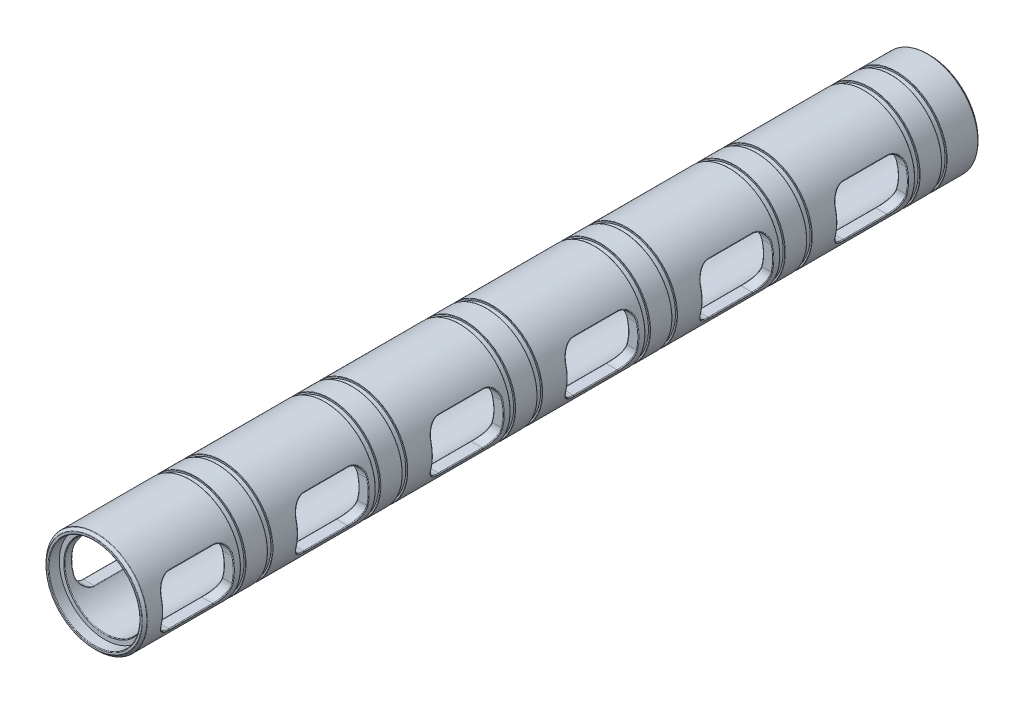
SolidWorks part; units mm, degrees
note: '?' marks a value the reader was unsure of.
ref_plane "Front Plane" through (0, 0, 0) normal (0, 0, 1) x (1, 0, 0)
ref_plane "Top Plane" through (0, 0, 0) normal (0, 1, 0) x (1, 0, 0)
ref_plane "Right Plane" through (0, 0, 0) normal (1, 0, 0) x (0, 0, -1)
ref_axis "Axis1" through (0, 0, -12.15) along (0, 0, 1)?
sketch "Sketch1" plane through (0, 0, 0) normal (0, 0, 1) x (1, 0, 0)
  circle A0 centre (0, 0) radius 15
  circle A1 centre (0, 0) radius 12
  dimension "D1" = 30
  dimension "D2" = 24
extrude "Extrude1" add sketch "Sketch1" along normal blind 248
sketch "Sketch2" plane through (0, 0, 248) normal (0, 0, 1) x (1, 0, 0)
  circle A0 centre (0, 0) radius 13.5
  dimension "D1" = 27
extrude "Cut-Extrude1" cut sketch "Sketch2" against normal blind 3.2
sketch "Sketch3" plane through (0, 0, 0) normal (0, 0, -1) x (-1, 0, 0)
  circle A0 centre (0, 0) radius 13.5
  dimension "D1" = 27
extrude "Cut-Extrude2" cut sketch "Sketch3" against normal blind 3.2
chamfer "Chamfer1" distance 0.75 angle 45 2 edges at (15, 0, 0) (15, 0, 248)
fillet "Fillet1" radius 0.2 4 edges at (12, 0, 244.8) (13.5, 0, 248) (-12, 0, 3.2) (-13.5, 0, 0)
sketch "Sketch5" plane through (0, 0, 0) normal (0, 0, -1) x (-1, 0, 0)
  circle A0 centre (0, 0) radius 15
  circle A1 centre (0, 0) radius 14.5
  circle A2 centre (0, 0) radius 15 construction
  dimension "D1" = 29
extrude "Cut-Extrude3" cut sketch "Sketch5" along normal blind 1.5 from offset 11.5
sketch "Sketch6" plane through (0, 0, 0) normal (0, 0, -1) x (-1, 0, 0)
  circle A0 centre (0, 0) radius 15
  circle A1 centre (0, 0) radius 14.5
  circle A2 centre (0, 0) radius 14.5 construction
  circle A4 centre (0, 0) radius 15 construction
extrude "Cut-Extrude4" cut sketch "Sketch6" against normal blind 1.5 from offset 18
fillet "Fillet2" radius 0.1 4 edges at (-15, 0, 10) (-15, 0, 11.5) (-15, 0, 19.5) (-15, 0, 18)
sketch "Sketch7" plane through (0, 0, 0) normal (1, 0, 0) x (0, 0, -1)
  line L0 (-38.5, 7.5) -> (-25.5, 7.5)
  line L1 (-21.5, 3.5) -> (-21.5, -3.5)
  line L2 (-25.5, -7.5) -> (-38.5, -7.5)
  line L3 (-42.5, 3.5) -> (-42.5, -3.5)
  arc A0 (-25.5, -7.5) -> (-21.5, -3.5) centre (-25.5, -3.5) ccw
  arc A1 (-25.5, 7.5) -> (-21.5, 3.5) centre (-25.5, 3.5) cw
  arc A2 (-38.5, 7.5) -> (-42.5, 3.5) centre (-38.5, 3.5) ccw
  arc A3 (-38.5, -7.5) -> (-42.5, -3.5) centre (-38.5, -3.5) cw
  dimension "D4" = 4
  dimension "D1" = 7.5
  dimension "D2" = 21.5
  dimension "D3" = 21
  dimension "D5" = 7.5
extrude "Cut-Extrude5" cut sketch "Sketch7" along normal through all from offset 20
fillet "Fillet3" radius 0.2 32 edges at (9.3675, 7.5, 32) (10.1429, 6.4125, 22.7583) (12, 0, 21.5) (9.9105, -6.7662, 23.1909) (9.3675, -7.5, 32) (10.3635, -6.0497, 41.5821) (12, 0, 42.5) (11.9865, 0.5692, 35.7778) (-9.3675, 7.5, 32) (-9.6937, 7.0734, 23.7025) (-12, 0, 21.5) (-10.5955, -5.6334, 22.1164) (-9.3675, -7.5, 32) (-9.702, -7.0619, 40.3201) (-12, 0, 42.5) (-10.6111, 5.6041, 41.9019) (-13.8789, 5.6899, 41.8473) (15, 0, 42.5) (-13.4247, -6.6917, 40.9111) (12.9904, -7.5, 32) (-13.8706, -5.7102, 22.1661) (15, 0, 21.5) (-13.4182, 6.7046, 23.1061) (-12.9904, 7.5, 32) (14.9875, 0.6113, 35.7331) (-15, 0, 42.5) (13.731, -6.0382, 41.5915) (-12.9904, -7.5, 32) (13.5377, -6.4598, 22.8094) (-15, 0, 21.5) (13.9805, 5.4355, 21.9995) (12.9904, 7.5, 32)
fillet "Fillet4" radius 0.2 4 edges at (14.25, 0, 248) (15, 0, 0.75) (15, 0, 247.25) (14.25, 0, 0)
pattern_linear "LPattern1" count 6 spacing 40 along (0, 0, 1) of "Cut-Extrude3", "Cut-Extrude4", "Fillet2", "Cut-Extrude5", "Fillet3"
